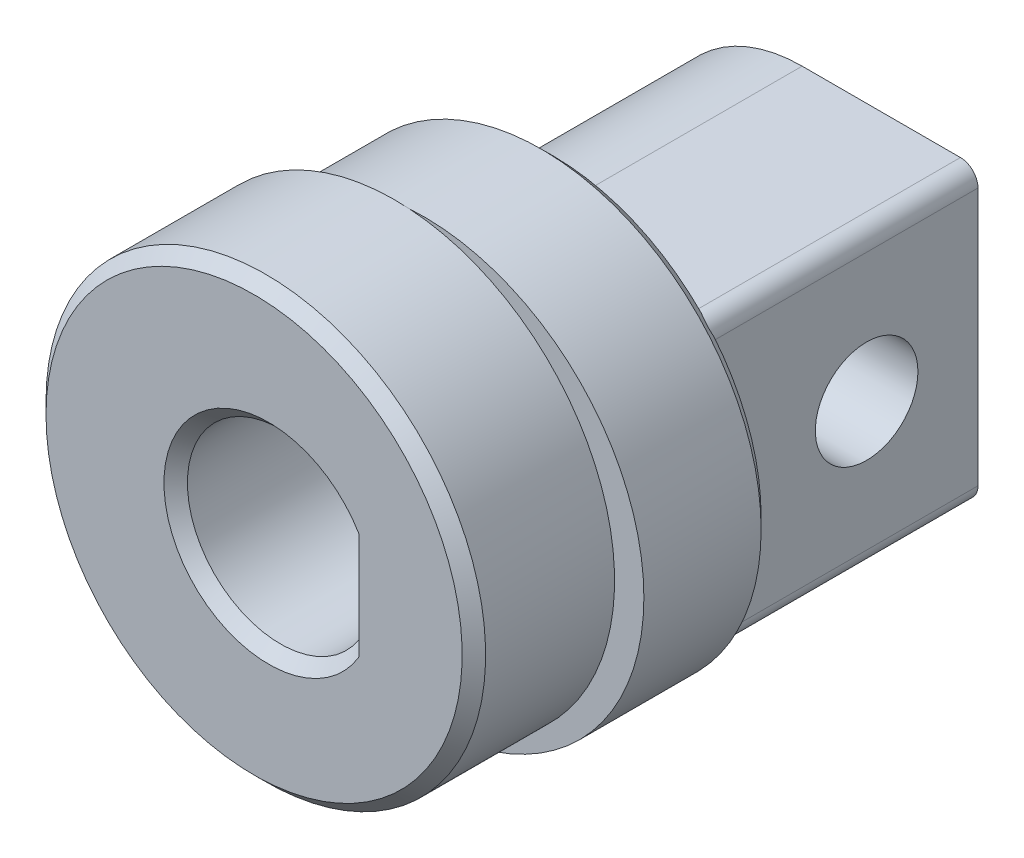
SolidWorks part; units mm, degrees
ref_plane "Ebene vorne" through (0, 0, 0) normal (0, 0, 1) x (1, 0, 0)
ref_plane "Ebene oben" through (0, 0, 0) normal (0, 1, 0) x (1, 0, 0)
ref_plane "Ebene rechts" through (0, 0, 0) normal (1, 0, 0) x (0, 0, -1)
ref_plane "Plane2" through (0, 0, 0.4) normal (0, 0, 1) x (1, 0, 0)
sketch "Sketch10" plane through (0, 0, 0.4) normal (0, 0, 1) x (1, 0, 0)
  circle A0 centre (0.5, 0) radius 7.5
  dimension "D1" = 15
  dimension "D2" = 0.5
extrude "Boss-Extrude4" add sketch "Sketch10" along normal blind 4.2 and the other way blind 0.2
sketch "Sketch11" plane through (0, 0, 0.2) normal (0, 0, -1) x (-1, 0, 0)
  line L0 (-6, -4.4) -> (-6, 4.4)
  line L1 (-5.4, 5) -> (0, 5)
  line L2 (0, -5) -> (-5.4, -5)
  arc A2 (0, 5) -> (0, -5) centre (0, 0) cw
  arc A3 (-6, 4.4) -> (-5.4, 5) centre (-5.4, 4.4) cw
  arc A4 (-5.4, -5) -> (-6, -4.4) centre (-5.4, -4.4) cw
  dimension "D1" = 5
  dimension "D3" = 0.6
  dimension "D2" = 6
extrude "Boss-Extrude5" add sketch "Sketch11" along normal blind 9
ref_plane "Plane3" through (0, 0, 4.6) normal (0, 0, -1) x (-1, 0, 0)
sketch "Sketch16" plane through (0, 0, 4.6) normal (0, 0, -1) x (-1, 0, 0)
  circle A0 centre (0.5, 0) radius 7.5
  dimension "D1" = 15
  dimension "D2" = 0.5
extrude "Boss-Extrude6" add sketch "Sketch16" against normal blind 4.8
sketch "Sketch17" plane through (0, 0, 9.4) normal (0, 0, 1) x (1, 0, 0)
  line L0 (2.675, -1.7103) -> (2.675, 1.7103)
  line L1 (-3.175, 0) -> (-3.175, 1.4955) construction
  arc A0 (2.675, 1.7103) -> (2.675, -1.7103) centre (0, 0) ccw
  dimension "D1" = 3.175
  dimension "D2" = 5.85
extrude "Cut-Extrude2" cut sketch "Sketch17" against normal through all
hole_wizard "Ø3.5 (3.5) Diameter Hole0" positions "Sketch19" profile "Sketch18" hole size "Ø3.5" standard "ANSI Metric"
sketch "Sketch19" plane through (6, 0, 0) normal (1, 0, 0) x (0, 0, -1)
  point P0 (5, 0)
sketch "Sketch18" plane through (6, 0, -5) normal (0, 1, 0) x (0, 0, -1)
  line L0 (0, 0) -> (0, 5.0515)
  line L1 (0, 5.0515) -> (1.75, 4)
  line L2 (1.75, 4) -> (1.75, 0)
  line L5 (1.75, 0) -> (0, 0)
  line L10 (0, 5.0515) -> (-1.75, 4) construction
  line L11 (0, -6.35) -> (0, 107.95) construction
  dimension "Hole Dia." = 3.5
  dimension "Hole Depth" = 4
  dimension "Drill Angle" = 118
chamfer "Chamfer2" distance 0.4 angle 45 6 edges at (-8, 0, 9.4) (8, 0, 0.2) (-3.175, 0, 9.4) (2.675, 0, 9.4) (2.675, 0, -8.8) (-3.175, 0, -8.8)
